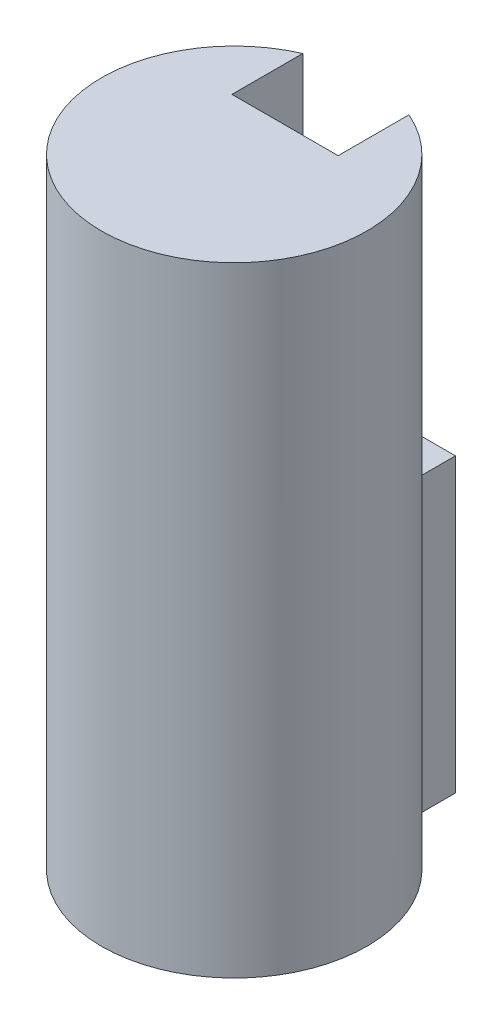
SolidWorks part; units mm, degrees
ref_plane "정면" through (0, 0, 0) normal (0, 0, 1) x (1, 0, 0)
ref_plane "윗면" through (0, 0, 0) normal (0, 1, 0) x (1, 0, 0)
ref_plane "우측면" through (0, 0, 0) normal (1, 0, 0) x (0, 0, -1)
sketch "스케치1" plane through (0, 0, 0) normal (0, 1, 0) x (1, 0, 0)
  line L0 (-1, 2.8284) -> (-1, 4)
  line L1 (-1, 4) -> (1, 4)
  line L2 (1, 4) -> (1, 2.8284)
  circle A0 centre (0, 0) radius 3
  dimension "D1" = 6
  dimension "D2" = 4
  dimension "D3" = 1
  dimension "D4" = 2
extrude "보스-돌출2" add sketch "스케치1" along normal blind 14 contours A0 region at (0, 0, 0)
extrude "보스-돌출3" add sketch "스케치1<3>" along normal blind 6.6 contours A0 L2 L1 L0 region at (0, 0, -3.4705)
sketch "스케치1<3>" plane through (0, 0, 0) normal (0, 1, 0) x (1, 0, 0) same geometry as "스케치1"
sketch "스케치2" plane through (0, 14, 0) normal (0, 1, 0) x (1, 0, 0)
  line L5 (-1.2, 1.1495) -> (1.2, 1.1495)
  line L6 (1.2, 1.1495) -> (1.2, 2.7495)
  line L7 (-1.2, 1.1495) -> (-1.2, 2.7495)
  line L8 (0, 0) -> (0, 1.1495) construction
  line L9 (-1.2, 2.7495) -> (0, 4.828)
  line L10 (0, 4.828) -> (1.2, 2.7495)
  circle A0 centre (0, 0) radius 3 construction
  dimension "D1" = 1.6
  dimension "D5" = 2.4
  dimension "D6" = 60
  dimension "D7" = 150
extrude "컷-돌출1" cut sketch "스케치2" against normal blind 4
